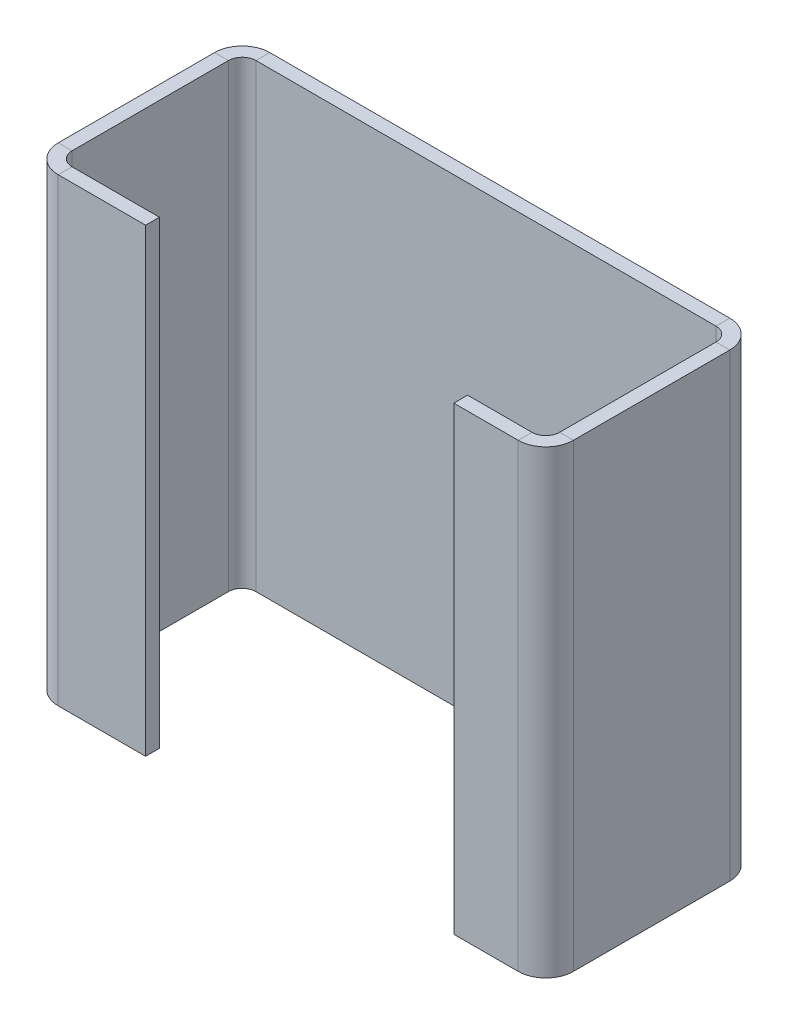
SolidWorks part; units mm, degrees
note: The reader was unsure of these and kept them because the rebuilt part matched: flange length of "Edge-Flange1", "Edge-Flange2", "Edge-Flange6", "Edge-Flange7".
ref_plane "Front Plane" through (0, 0, 0) normal (0, 0, 1) x (1, 0, 0)
ref_plane "Top Plane" through (0, 0, 0) normal (0, 1, 0) x (1, 0, 0)
ref_plane "Right Plane" through (0, 0, 0) normal (1, 0, 0) x (0, 0, -1)
other "Center of Mass"
sketch "Sketch1" plane through (0, 0, 0) normal (0, 0, 1) x (1, 0, 0)
  line L0 (50, 50) -> (-50, -50) construction
  line L1 (-50, 50) -> (50, 50)
  line L2 (-50, 50) -> (-50, -50)
  line L3 (-50, -50) -> (50, -50)
  line L4 (50, 50) -> (50, -50)
  point P4 (0, 0)
  dimension "D1" = 100
  dimension "D2" = 100
base flange "Base-Flange1" sketch "Sketch1" thickness 3 reverse thickness direction no parameters "D1"=3
edge flange "Edge-Flange1" sketch "Sketch8" flange angle 90 flange length 40 flange position bend outside bend radius 3 thickness 3 relief rectangular parameters "D6"=10
sketch "Sketch8" plane through (-50, 0, 0) normal (-1, 0, 0) x (0, -1, 0)
  line L0 (-50, 0) -> (50, 0) construction
  line L1 (-50, 0) -> (50, 0)
  line L2 (-50, 0) -> (-50, 37)
  line L3 (-50, 37) -> (50, 37)
  line L4 (50, 37) -> (50, 0)
bend "EdgeBend1" bend radius 3 bend angle 90 parameters "D5"=1
edge flange "Edge-Flange2" sketch "Sketch11" flange angle 90 flange length 40 flange position bend outside bend radius 3 thickness 3 relief rectangular parameters "D6"=10
sketch "Sketch11" plane through (50, 0, 0) normal (-1, 0, 0) x (0, -1, 0)
  line L1 (50, 0) -> (-50, 0) construction
  line L2 (-50, 0) -> (-50, 37)
  line L3 (-50, 37) -> (50, 37)
  line L4 (50, 37) -> (50, 0)
  line L5 (50, 0) -> (-50, 0)
bend "EdgeBend2" bend radius 3 bend angle 90 parameters "D5"=2
edge flange "Edge-Flange6" sketch "Sketch21" flange angle 90 flange length 25 flange position bend outside bend radius 3 thickness 3 relief rectangular parameters "D6"=10
sketch "Sketch21" plane through (-53, 0, 37) normal (0, 0, 1) x (0, -1, 0)
  line L0 (50, 0) -> (-50, 0) construction
  line L1 (50, 0) -> (-50, 0)
  line L2 (-50, 0) -> (-50, 22)
  line L3 (-50, 22) -> (50, 22)
  line L4 (50, 22) -> (50, 0)
bend "EdgeBend3" bend radius 3 bend angle 90 parameters "D5"=3
edge flange "Edge-Flange7" sketch "Sketch24" flange angle 90 flange length 20 flange position bend outside bend radius 3 thickness 3 relief rectangular parameters "D6"=10
sketch "Sketch24" plane through (53, 0, 37) normal (0, 0, 1) x (0, 1, 0)
  line L0 (-50, 0) -> (50, 0) construction
  line L1 (-50, 0) -> (50, 0)
  line L2 (-50, 0) -> (-50, 17)
  line L3 (-50, 17) -> (50, 17)
  line L4 (50, 17) -> (50, 0)
bend "EdgeBend4" bend radius 3 bend angle 90 parameters "D5"=4
sketch "Bend-Lines1" [suppressed] plane through (0, 0, 0) normal (0, 1, 0) x (1, 0, 0)
sketch "Bounding-Box1" [suppressed] plane through (0, 0, 0) normal (0, 1, 0) x (1, 0, 0)
sheet metal parameters "Sheet-Metal1" thickness 3 parameters "D1"=3
flat pattern "Flat-Pattern1" [suppressed]
sketch "Bend-Lines2" plane through (0, 0, 0) normal (0, 1, 0) x (1, 0, 0)
sketch "Bounding-Box2" [suppressed] plane through (0, 0, 0) normal (0, 1, 0) x (1, 0, 0)
sheet metal parameters "Sheet-Metal2" thickness 3 parameters "D1"=3
flat pattern "Flat-Pattern1" [suppressed]
sketch "Bend-Lines2" plane through (0, 0, 0) normal (0, 1, 0) x (1, 0, 0)
sketch "Bounding-Box2" [suppressed] plane through (0, 0, 0) normal (0, 1, 0) x (1, 0, 0)
bend of the flat pattern "Flatten-<EdgeBend1>1"
sheet metal parameters "Sheet-Metal3" thickness 3 parameters "D1"=3
flat pattern "Flat-Pattern1" [suppressed]
sketch "Bend-Lines2" plane through (0, 0, 0) normal (0, 1, 0) x (1, 0, 0)
sketch "Bounding-Box2" [suppressed] plane through (0, 0, 0) normal (0, 1, 0) x (1, 0, 0)
bend of the flat pattern "Flatten-<EdgeBend1>1"
bend of the flat pattern "Flatten-<EdgeBend2>1"
sheet metal parameters "Sheet-Metal4" thickness 3 parameters "D1"=3
flat pattern "Flat-Pattern1" [suppressed]
sketch "Bend-Lines2" plane through (0, 0, 0) normal (0, 1, 0) x (1, 0, 0)
sketch "Bounding-Box2" [suppressed] plane through (0, 0, 0) normal (0, 1, 0) x (1, 0, 0)
bend of the flat pattern "Flatten-<EdgeBend1>1"
bend of the flat pattern "Flatten-<EdgeBend2>1"
bend of the flat pattern "Flatten-<EdgeBend3>1"
sheet metal parameters "Sheet-Metal5" thickness 3 parameters "D1"=3
flat pattern "Flat-Pattern1" [suppressed]
sketch "Bend-Lines2" plane through (0, 0, 0) normal (0, 1, 0) x (1, 0, 0)
sketch "Bounding-Box2" [suppressed] plane through (0, 0, 0) normal (0, 1, 0) x (1, 0, 0)
bend of the flat pattern "Flatten-<EdgeBend1>1"
bend of the flat pattern "Flatten-<EdgeBend2>1"
bend of the flat pattern "Flatten-<EdgeBend3>1"
bend of the flat pattern "Flatten-<EdgeBend4>1"
